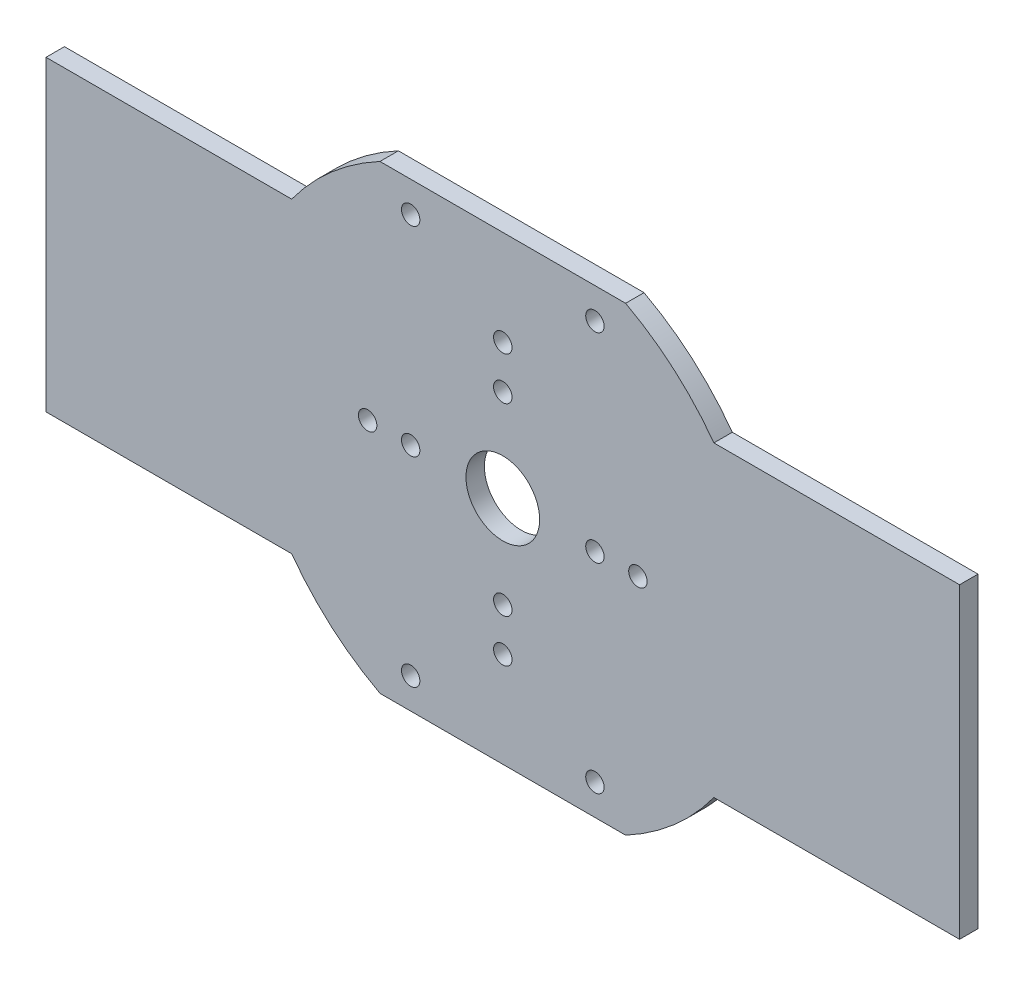
SolidWorks part; units mm, degrees
ref_plane "前视基准面" through (0, 0, 0) normal (0, 0, 1) x (1, 0, 0)
ref_plane "上视基准面" through (0, 0, 0) normal (0, 1, 0) x (1, 0, 0)
ref_plane "右视基准面" through (0, 0, 0) normal (1, 0, 0) x (0, 0, -1)
sketch "草图1" plane through (0, 0, 0) normal (0, 0, 1) x (1, 0, 0)
  line L1 (0, 0) -> (40, 0)
  line L2 (0, 0) -> (0, -75)
  line L3 (0, -75) -> (40, -75)
  line L4 (40, 0) -> (40, -75)
  circle A0 centre (20, -37.5) radius 42.5
  circle A1 centre (5, -5) radius 1.5
  circle A2 centre (35, -5) radius 1.5
  circle A3 centre (5, -70) radius 1.5
  circle A4 centre (35, -70) radius 1.5
  dimension "D3" = 5
  dimension "D5" = 5
  dimension "D7" = 5
  dimension "D1" = 40
  dimension "D2" = 75
  dimension "D4" = 5
  dimension "D6" = 5
  dimension "D8" = 5
extrude "凸台-拉伸7" add sketch "草图1" along normal mid plane 3 contours A0
extrude "切除-拉伸24" cut sketch "草图1<12>" against normal mid plane 3 contours L1 A0 region at (20, 2.0104, 0)
sketch "草图1<12>" plane through (0, 0, 0) normal (0, 0, 1) x (1, 0, 0) same geometry as "草图1"
extrude "切除-拉伸25" cut sketch "草图1<13>" against normal mid plane 3 contours L3 A0 region at (20, -77.0104, 0)
sketch "草图1<13>" plane through (0, 0, 0) normal (0, 0, 1) x (1, 0, 0) same geometry as "草图1"
extrude "切除-拉伸26" cut sketch "草图1<14>" against normal mid plane 3 contours A1
sketch "草图1<14>" plane through (0, 0, 0) normal (0, 0, 1) x (1, 0, 0) same geometry as "草图1"
extrude "切除-拉伸27" cut sketch "草图1<15>" against normal mid plane 3 contours A2
sketch "草图1<15>" plane through (0, 0, 0) normal (0, 0, 1) x (1, 0, 0) same geometry as "草图1"
extrude "切除-拉伸28" cut sketch "草图1<16>" against normal mid plane 3 contours A3
sketch "草图1<16>" plane through (0, 0, 0) normal (0, 0, 1) x (1, 0, 0) same geometry as "草图1"
extrude "切除-拉伸29" cut sketch "草图1<17>" against normal mid plane 3 contours A4
sketch "草图1<17>" plane through (0, 0, 0) normal (0, 0, 1) x (1, 0, 0) same geometry as "草图1"
sketch "草图10" plane through (0, 0, 1.5) normal (0, 0, 1) x (1, 0, 0)
  circle A1 centre (20, -15.5) radius 1.5
  circle A2 centre (-2, -37.5) radius 1.5
  circle A3 centre (42, -37.5) radius 1.5
  circle A4 centre (20, -59.5) radius 1.5
  circle A6 centre (20, -22.5) radius 1.5
  circle A7 centre (5, -37.5) radius 1.5
  circle A8 centre (20, -52.5) radius 1.5
  circle A9 centre (35, -37.5) radius 1.5
extrude "切除-拉伸31" cut sketch "草图10" against normal through all
sketch "草图11" plane through (0, 0, 1.5) normal (0, 0, 1) x (1, 0, 0)
  circle A0 centre (20, -37.5) radius 6
extrude "切除-拉伸32" cut sketch "草图11" against normal through all
sketch "草图19" plane through (0, 0, 1.5) normal (0, 0, 1) x (1, 0, 0)
  line L0 (-14.3693, -12.5) -> (-14.3693, -62.5)
  line L1 (-14.3693, -12.5) -> (54.3693, -12.5)
  line L2 (-14.3693, -62.5) -> (54.3693, -62.5)
  line L3 (54.3693, -62.5) -> (54.3693, -12.5)
  circle A0 centre (20, -37.5) radius 42.5 construction
  arc M15 (0, 0) -> (0, -75) centre (20, -37.5) ccw
  arc M17 (40, -75) -> (40, 0) centre (20, -37.5) ccw
  dimension "D1" = 50
extrude "切除-拉伸35" cut sketch "草图19" against normal mid plane 10 contours L0 M15 | L3 M17 region at (-17.6498, -37.5, 1.5) region at (57.6498, -37.5, 1.5)
sketch "草图41" plane through (54.3693, 0, 0) normal (1, 0, 0) x (0, 0, -1)
  line L0 (-1.5, -12.5) -> (-1.5, -62.5)
  line L1 (-1.5, -62.5) -> (1.5, -62.5)
  line L2 (1.5, -62.5) -> (1.5, -12.5)
  line L3 (1.5, -12.5) -> (-1.5, -12.5)
extrude "凸台-拉伸14" add sketch "草图41" along normal blind 40
sketch "草图42" plane through (-14.3693, 0, 0) normal (-1, 0, 0) x (0, 0, 1)
  line L0 (-1.5, -12.5) -> (-1.5, -62.5)
  line L1 (-1.5, -62.5) -> (1.5, -62.5)
  line L2 (1.5, -62.5) -> (1.5, -12.5)
  line L3 (1.5, -12.5) -> (-1.5, -12.5)
extrude "凸台-拉伸15" add sketch "草图42" along normal blind 40
